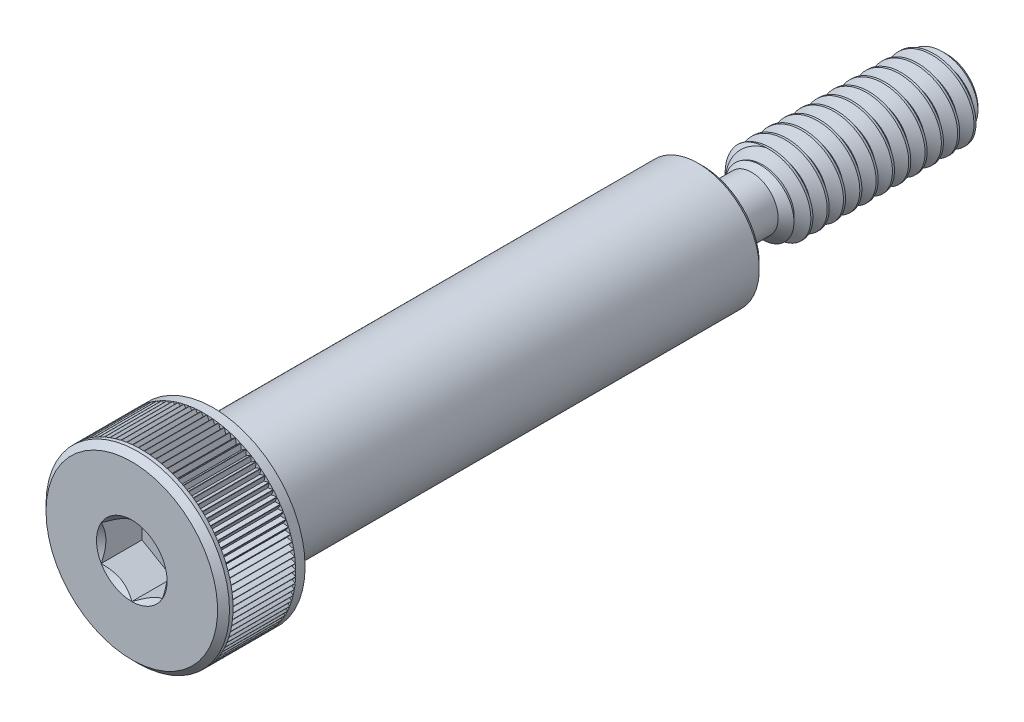
SolidWorks part; units mm, degrees
other "DetailItem1"
other "DetailItem2"
other "DetailItem5"
other "DetailItem6"
ref_plane "Front" through (0, 0, 0) normal (0, 0, 1) x (1, 0, 0)
ref_plane "Top" through (0, 0, 0) normal (0, 1, 0) x (1, 0, 0)
ref_plane "Right" through (0, 0, 0) normal (1, 0, 0) x (0, 0, -1)
sketch "Sketch1" plane through (0, 0, 0) normal (1, 0, 0) x (0, 0, -1)
  line L0 (0, 7.1437) -> (6.35, 7.1437) construction
  line L1 (6.35, 7.1437) -> (6.35, 4.4053) construction
  line L2 (7.9772, 4.7625) -> (44.45, 4.7625) construction
  line L3 (7.9772, -4.7625) -> (44.45, -4.7625) construction
  line L4 (44.45, 3.175) -> (63.5, 3.175) construction
  line L5 (63.5, 3.175) -> (63.5, 0) construction
  line L6 (44.45, 0) -> (0, 0) construction
  line L7 (0, 0) -> (0, 7.1437) construction
  line L8 (0, 7.1437) -> (0, -7.1438) construction
  line L9 (63.5, 3.175) -> (63.5, -3.175) construction
  line L10 (44.45, 4.7625) -> (44.45, -4.7625) construction
  line L11 (63.5, -3.175) -> (61.8222, -3.175) construction
  line L12 (44.45, 4.7625) -> (44.45, 0) construction
  line L13 (6.35, 4.4053) -> (7.62, 4.4053) construction
  line L14 (7.62, 4.4053) -> (7.9772, 4.7625) construction
  line L15 (63.5, 0) -> (44.45, 0) construction
  line L16 (7.62, -4.4053) -> (7.9772, -4.7625) construction
  line L17 (6.35, -4.4053) -> (7.62, -4.4053) construction
  line L18 (0, -7.1438) -> (6.35, -7.1438) construction
  line L19 (6.35, -7.1438) -> (6.35, -4.4053) construction
  line L20 (63.5, 4.7625) -> (61.595, 4.7625) construction
  line L21 (63.5, -4.7625) -> (61.595, -4.7625) construction
  line L22 (63.5, 0) -> (82.55, 0) construction
  line L23 (25.4, 0) -> (25.4, 7.1438) construction
  line L24 (63.5, -4.7625) -> (63.5, 4.7625) construction
  line L25 (0, -2.3813) -> (0, 2.3813) construction
  line L26 (63.4206, 3.3125) -> (64.6906, 3.3125) construction
  line L27 (64.6906, 3.3125) -> (64.0556, 2.2126) construction
  line L28 (64.0556, 2.2126) -> (63.4206, 3.3125) construction
  line L29 (64.0556, 2.2126) -> (64.0556, 2.3501) construction
  line L30 (64.0556, 3.3125) -> (64.0556, 3.175) construction
  line L31 (64.6113, 3.175) -> (63.5, 3.175) construction
  line L32 (63.9763, 2.3501) -> (64.135, 2.3501) construction
  line L33 (64.0556, 3.2437) -> (64.6509, 3.2437) construction
  line L34 (64.0556, 3.2437) -> (63.4603, 3.2437) construction
  line L35 (7.9772, 4.7625) -> (7.9772, -4.7625) construction
  line L36 (44.0928, 4.7625) -> (44.45, 4.4053) construction
  line L37 (44.0928, 4.7625) -> (44.0928, 0) construction
  point P2 (7.3025, 0)
  point P8 (61.595, -3.175)
  point P12 (44.45, 0)
  point P15 (43.4975, 0)
  point P31 (9.1123, 0)
  point P32 (41.6878, 0)
  point P34 (63.5, 0)
  point P37 (0, 0)
  dimension "D1" = 1.905
  dimension "D2" = 1.6778
  dimension "D3" = 135
  dimension "D4" = 1.27
  dimension "D5" = 0.3572
  dimension "D6" = 19.05
  dimension "D7" = 36.195
  dimension "D8" = 32.5755
  dimension "D9" = 0.1588
  dimension "Shoulder Lg" = 38.1
  dimension "D10" = 45
sketch "Sketch13" plane through (0, 0, 0) normal (1, 0, 0) x (0, 0, -1)
  line L0 (0, 0) -> (0, 7.1437)
  line L1 (0, 7.1437) -> (6.35, 7.1437)
  line L2 (6.35, 7.1437) -> (6.35, 4.4053)
  line L3 (6.35, 4.4053) -> (7.62, 4.4053)
  line L4 (44.45, 0) -> (44.45, 4.4053)
  line L5 (7.62, 4.4053) -> (7.9772, 4.7625)
  line L7 (44.45, 4.7625) -> (44.45, 0) construction
  line L8 (44.45, 4.7625) -> (44.45, -4.7625) construction
  line L9 (44.45, 0) -> (0, 0) construction
  line L10 (44.45, 4.4053) -> (44.0928, 4.7625)
  line L12 (7.9772, 4.7625) -> (44.0928, 4.7625)
  line L13 (0, 0) -> (44.45, 0)
  line L14 (7.9772, 4.7625) -> (44.45, 4.7625) construction
  line L18 (63.5, 4.7625) -> (63.5, -4.7625) construction
  dimension "D1" = 38.1
  dimension "D2" = 45
  dimension "D3" = 9.525
revolve "Revolve1" add sketch "Sketch13" angle 360 about L9
sketch "Sketch12" plane through (0, 0, -44.45) normal (0, 0, -1) x (-1, 0, 0)
  circle A0 centre (0, 0) radius 3.175
extrude "Boss-Extrude1" add sketch "Sketch12" along normal up to vertex (19.05 mm away) up to point (0, 0, -63.5)
ref_plane "Plane1" through (0, 0, -63.5) normal (0, 0, 1) x (1, 0, 0)
sketch "Sketch3" plane through (0, 0, -63.5) normal (0, 0, 1) x (1, 0, 0)
  circle A0 centre (0, 0) radius 3.175
sketch "Sketch5" plane through (0, 0, 0) normal (1, 0, 0) x (0, 0, -1)
  line L0 (44.45, 3.175) -> (49.3713, 3.175)
  line L1 (49.3713, 3.175) -> (48.26, 2.0638)
  line L2 (48.26, 2.0638) -> (44.45, 2.0637)
  line L3 (44.45, 3.175) -> (44.45, 2.0637)
  line L4 (44.45, 3.175) -> (63.5, 3.175) construction
  line L5 (44.45, 4.7625) -> (44.45, 0) construction
  line L6 (44.45, 4.7625) -> (44.45, -4.7625) construction
  line L7 (63.5, 0) -> (44.45, 0) construction
  line L8 (63.5, -3.175) -> (63.5, 3.175) construction
  dimension "D4" = 3.81
  dimension "D1" = 45
  dimension "D2" = 15.24
  dimension "D3" = 2.0638
revolve "Cut-Revolve1" cut sketch "Sketch5" angle 360 mid plane about L6
chamfer "Chamfer1" distance 0.7937 angle 45 1 edges at (-3.175, 0, -63.5)
chamfer "Chamfer2" distance 0.4643 angle 45 1 edges at (-7.1437, 0, 0)
fillet "Fillet1" radius 0.3175 1 edges at (0, 2.0637, -44.45)
sketch "Sketch10" plane through (0, 0, 0) normal (1, 0, 0) x (0, 0, -1)
  line L0 (0.4643, 0) -> (5.8857, 0) construction
  line L1 (6.35, -7.1437) -> (6.35, 7.1437) construction
  line L2 (0.4643, -7.1437) -> (0.4643, 7.1437) construction
  line L3 (0.4643, 0) -> (0, 0) construction
  line L4 (5.8857, 0) -> (6.35, 0) construction
  point P6 (3.175, 0)
  dimension "D1" = 5.4213
ref_plane "Plane2" through (0, 0, -3.175) normal (0, 0, 1) x (1, 0, 0)
sketch "Sketch8" plane through (0, 0, 0) normal (0, 0, 1) x (1, 0, 0)
  line L1 (2.3812, 1.3748) -> (0, 2.7496)
  line L2 (0, 2.7496) -> (-2.3813, 1.3748)
  line L3 (-2.3813, 1.3748) -> (-2.3813, -1.3748)
  line L4 (-2.3813, -1.3748) -> (0, -2.7496)
  line L5 (0, -2.7496) -> (2.3812, -1.3748)
  line L6 (2.3812, -1.3748) -> (2.3812, 1.3748)
  circle A0 centre (0, 0) radius 2.3813 construction
extrude "Cut-Extrude2" cut sketch "Sketch8" against normal blind 3.175
sketch "Sketch9" plane through (0, 0, 0) normal (0, 0, 1) x (1, 0, 0)
  circle A0 centre (0, 0) radius 2.7496
extrude "Cut-Extrude4" cut sketch "Sketch9" against normal blind 3.175 draft 45
sketch "Sketch16" plane through (0, 0, 0) normal (0, 1, 0) x (1, 0, 0)
  line L0 (0, 25.4) -> (-4.7625, 25.4) construction
  line L1 (-4.7625, 44.0928) -> (-4.7625, 7.9772) construction
  line L2 (0, 41.6878) -> (-4.7625, 41.6878) construction
  line L3 (0, 25.4) -> (0, 41.6878) construction
  line L4 (0, 33.5439) -> (0, 41.6878) construction
  line L5 (0, 41.6878) -> (0, 37.6158) construction
  line L6 (0, 37.6158) -> (-4.7625, 37.6158) construction
  line L7 (0, 7.9772) -> (-4.7625, 7.9772) construction
  line L8 (-4.7625, 7.9772) -> (4.7625, 7.9772) construction
  line L9 (0, 44.45) -> (4.7625, 44.45) construction
  point P0 (0, 25.4)
  point P2 (0, 41.6878)
  point P11 (0, 7.9772)
sketch "reference 1" plane through (0, 0, -6.35) normal (0, 0, -1) x (-1, 0, 0)
  circle A1 centre (0, 0) radius 7.1437
ref_axis "Center Axis 1" through (0, 0, -7.9772) along (0, 0, -1)
ref_plane "Contact Plane 1" through (0, 0, -63.5) normal (0, 0, -1) x (-1, 0, 0)
ref_plane "Contact Plane 2" through (0, 0, -6.35) normal (0, 0, -1) x (-1, 0, 0)
ref_plane "Plane3" through (0, 0, -44.45) normal (0, 0, 1) x (1, 0, 0)
split "Split1" trim tools "Plane3" bodies to split 118 resulting bodies 127 128
sketch "Sketch15" plane through (0, 0, -63.5) normal (0, 0, -1) x (-1, 0, 0)
  circle A0 centre (0, 0) radius 3.175
curve "Helix/Spiral1" pitch 1.27 height 17.78 radius 3.175 centre (0, 0, -63.5) axis (0, 0, 1) start towards (0, 1, 0)
sketch "Sketch4" plane through (0, 0, 0) normal (1, 0, 0) x (0, 0, -1)
  line L0 (63.9763, 2.3501) -> (64.135, 2.3501) construction
  line L1 (64.6906, 3.3125) -> (64.0556, 2.2126) construction
  line L3 (64.0556, 3.2437) -> (64.6509, 3.2437) construction
  line L4 (64.0556, 3.2437) -> (63.4603, 3.2437) construction
  line L5 (64.0556, 2.2126) -> (63.4206, 3.3125) construction
  line L6 (63.9763, 2.3501) -> (64.135, 2.3501)
  line L7 (64.6509, 3.2437) -> (64.135, 2.3501)
  line L8 (64.0556, 3.2437) -> (64.6509, 3.2437)
  line L9 (64.0556, 3.2437) -> (63.4603, 3.2437)
  line L10 (63.9763, 2.3501) -> (63.4603, 3.2437)
sweep "Cut-Sweep1" cut profiles "Sketch4" path "Helix/Spiral1" align with end faces yes
sketch "Sketch14" plane through (0, 0, -44.45) normal (0, 0, -1) x (-1, 0, 0)
  line L0 (0, -4.7625) -> (0, 4.7625) construction
  circle A0 centre (0, 0) radius 1.5875
  dimension "D1" = 3.175
extrude "Boss-Extrude2" add sketch "Sketch14" along normal up to vertex (17.145 mm away) up to point (0, 4.7625, -61.595)
sketch "Sketch11" plane through (0, 0, -3.175) normal (0, 0, 1) x (1, 0, 0)
  line L0 (0, 6.7723) -> (0, 7.1437) construction
  line L1 (0, 6.7723) -> (0.2145, 7.1437)
  line L2 (0, 6.7723) -> (-0.2145, 7.1437)
  line L3 (-0.2145, 7.1437) -> (0.2145, 7.1437)
  line L4 (0, 0) -> (-0.2145, 7.1437) construction
  line L5 (0.2145, 7.1437) -> (0, 0) construction
  circle A2 centre (0, 0) radius 7.1437 construction
  point P8 (2.3908, 0.7309)
  dimension "D1" = 0.3715
  dimension "D2" = 3.439
extrude "Cut-Extrude5" cut sketch "Sketch11" along normal blind 2.4396 and the other way blind 2.4396
pattern_circular "CirPattern1" count 99 over 360 about axis through (0, 0, -44.45) along (0, 0, 1) of "Cut-Extrude5" reverse direction yes
equation "\"D1@Chamfer1\" = \"Thread Dia@Sketch1\" * .125"
equation "\"D1@Cut-Extrude2\"= \"Head Ht@Sketch1\" * .5"
equation "\"D1@Cut-Extrude4\" = \"D1@Cut-Extrude2\""
equation "\"D1@Chamfer2\"=\"Head Dia@Sketch1\" * .0325"
equation "\"D1@Sketch1\"=\"Pitch@Sketch1\"*1.5"
equation "\"D1@Sketch11\"=\"D1@Chamfer2\"*.8"
equation "\"D4@Sketch5\"=\"Thread Lg@Sketch1\"*0.2"
equation "\"D3@Sketch5\"=(\"Thread Dia@Sketch1\"*0.65)/2"
equation "\"D1@Fillet1\"=\"Pitch@Sketch1\"*.25"
equation "\"D1@Cut-Extrude5\"=\"D1@Sketch10\"*.45"
equation "\"D1@CirPattern1\"=(360/(\"D2@Sketch11\"))-6"
equation "\"D4@Sketch1\"=\"Head Ht@Sketch1\"*0.2"
equation "\"D5@Sketch1\"=\"Head Dia@Sketch1\"*0.025"
equation "\"D6@Sketch1\"=\"Shoulder Lg@Sketch1\"/2"
equation "\"D7@Sketch1\"=\"Shoulder Lg@Sketch1\"*0.95"
equation "\"D8@Sketch1\"=\"D7@Sketch1\"*0.9"
equation "\"D2@Cut-Extrude5\"=\"D1@Sketch10\"*.45"
equation "\"D9@Sketch1\"=\"Pitch@Sketch1\"/8"
equation "\"D1@Sketch14\"=\"Thread Dia@Sketch1\"*.5"
equation "\"D4@Helix/Spiral1\"=\"Pitch@Sketch1\""
equation "\"D3@Helix/Spiral1\"=\"Thread Lg@Sketch1\"-\"Pitch@Sketch1\""
